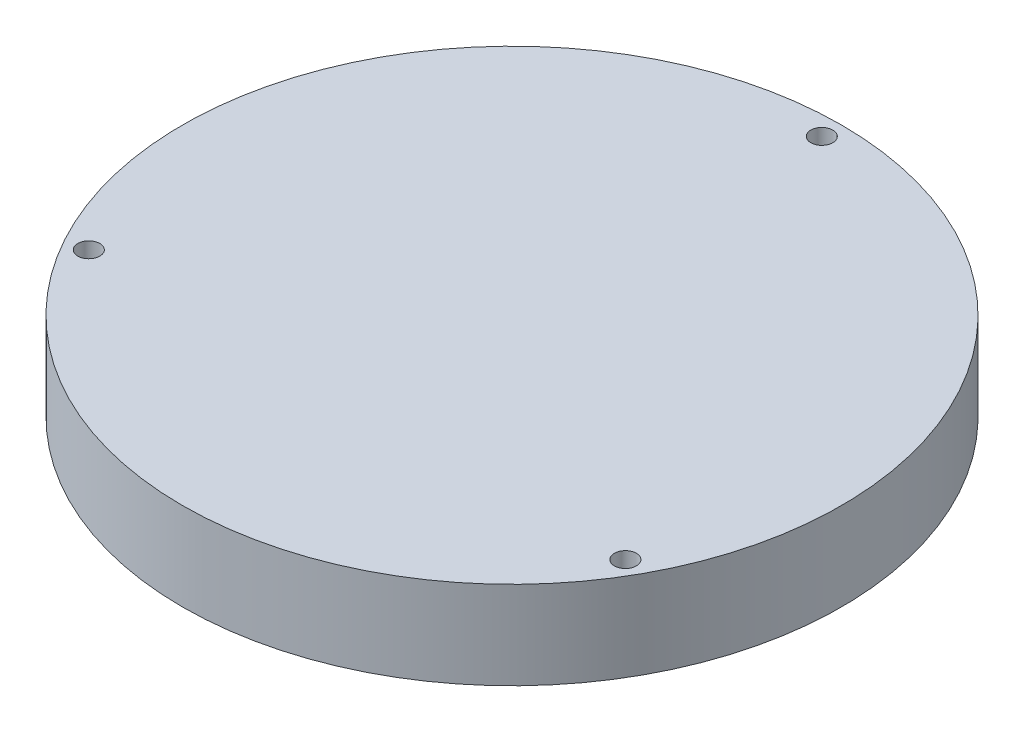
SolidWorks part; units mm, degrees
ref_plane "Front Plane" through (0, 0, 0) normal (0, 0, 1) x (1, 0, 0)
ref_plane "Top Plane" through (0, 0, 0) normal (0, 1, 0) x (1, 0, 0)
ref_plane "Right Plane" through (0, 0, 0) normal (1, 0, 0) x (0, 0, -1)
sketch "Sketch1" plane through (0, 0, 0) normal (0, 1, 0) x (1, 0, 0)
  circle A0 centre (0, 0) radius 95.25
  dimension "D1" = 190.5
extrude "Boss-Extrude1" add sketch "Sketch1" along normal mid plane 25.4
sketch "Sketch2" plane through (0, 12.7, 0) normal (0, 1, 0) x (1, 0, 0)
  line L0 (0, 0) -> (0, 109.4687) construction
  line L1 (0, 0) -> (96.8035, 55.8895) construction
  circle A0 centre (0, 0) radius 89.535 construction
  circle A1 centre (0, 0) radius 95.25 construction
  circle A2 centre (0, 89.535) radius 3.175
  point P9 (0, 0)
  dimension "D1" = 5.715
  dimension "D3" = 6.35
  dimension "D2" = 60
extrude "Cut-Extrude1" cut sketch "Sketch2" against normal through all
pattern_circular "CirPattern1" count 3 over 360 about axis through (0, 12.7, 0) along (0, -1, 0) of "Cut-Extrude1"
sketch "Sketch3" plane through (0, -12.7, 0) normal (0, -1, 0) x (-1, 0, 0)
  line L0 (0, 0) -> (-96.8035, 55.8895) construction
  circle A0 centre (-77.5396, 44.7675) radius 2.8448
  circle A1 centre (0, 0) radius 89.535 construction
  point P6 (0, 0)
  dimension "D1" = 5.6896
extrude "Cut-Extrude2" cut sketch "Sketch3" against normal up to surface (12.7 mm away) up to plane "Top Plane"
pattern_circular "CirPattern2" count 3 over 360 about axis through (0, 12.7, 0) along (0, -1, 0) of "Cut-Extrude2" reverse direction yes
